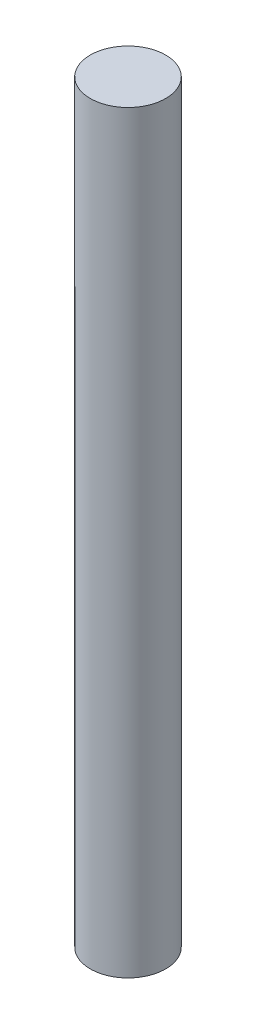
SolidWorks part; units mm, degrees
ref_plane "前视基准面" through (0, 0, 0) normal (0, 0, 1) x (1, 0, 0)
ref_plane "上视基准面" through (0, 0, 0) normal (0, 1, 0) x (1, 0, 0)
ref_plane "右视基准面" through (0, 0, 0) normal (1, 0, 0) x (0, 0, -1)
sketch "草图1" plane through (0, 0, 0) normal (0, 0, 1) x (1, 0, 0)
  line L1 (-3.75, 75) -> (3.75, 75)
  line L2 (-3.75, 75) -> (-3.75, -75)
  line L3 (-3.75, -75) -> (3.75, -75)
  line L4 (3.75, 75) -> (3.75, -75)
  line L5 (-3.75, 75) -> (3.75, -75) construction
  line L6 (-3.75, -75) -> (3.75, 75) construction
  point P0 (0, 0)
  dimension "D1" = 150
  dimension "D2" = 7.5
revolve "旋转1" add sketch "草图1" angle 360 about L4
sketch "草图2" plane through (0, 0, 0) normal (0, 0, 1) x (1, 0, 0)
  line L0 (-3.75, 75) -> (-27.95, 75)
  line L1 (-27.95, 75) -> (-27.95, -24)
  line L3 (-3.75, -82.3368) -> (1.25, -82.3368)
  line L4 (-27.95, -24) -> (-3.75, -24)
  line L22 (-3.75, 75) -> (1.25, 69.5)
  line L23 (-3.75, 64) -> (1.25, 69.5)
  line L24 (-3.75, 64) -> (1.25, 58.5)
  line L25 (1.25, 58.5) -> (-3.75, 53)
  line L26 (-3.75, 53) -> (1.25, 47.5)
  line L27 (1.25, 47.5) -> (-3.75, 42)
  line L28 (-3.75, 42) -> (1.25, 36.5)
  line L29 (1.25, 36.5) -> (-3.75, 31)
  line L30 (-3.75, 31) -> (1.25, 25.5)
  line L31 (1.25, 25.5) -> (-3.75, 20)
  line L32 (-3.75, 20) -> (1.25, 14.5)
  line L33 (1.25, 14.5) -> (-3.75, 9)
  line L34 (-3.75, 9) -> (1.25, 3.5)
  line L35 (-3.75, -2) -> (1.25, 3.5)
  line L36 (-3.75, -2) -> (1.25, -7.5)
  line L37 (1.25, -7.5) -> (-3.75, -13)
  line L38 (-3.75, -13) -> (1.25, -18.5)
  line L39 (1.25, -18.5) -> (-3.75, -24)
  dimension "D1" = 5
extrude "切除-拉伸1" cut sketch "草图2" against normal mid plane 2 contours L39 L38 L37 L36 L35 L34 L33 L32 L31 L30 L29 L28 L27 L26 L25 L24 L23 L22 L0 L1 L4 region at (-14.561, 25.5, 0)
ref_axis "基准轴1" through (1.25, 25.5, -1) along (0, 0, 1)
